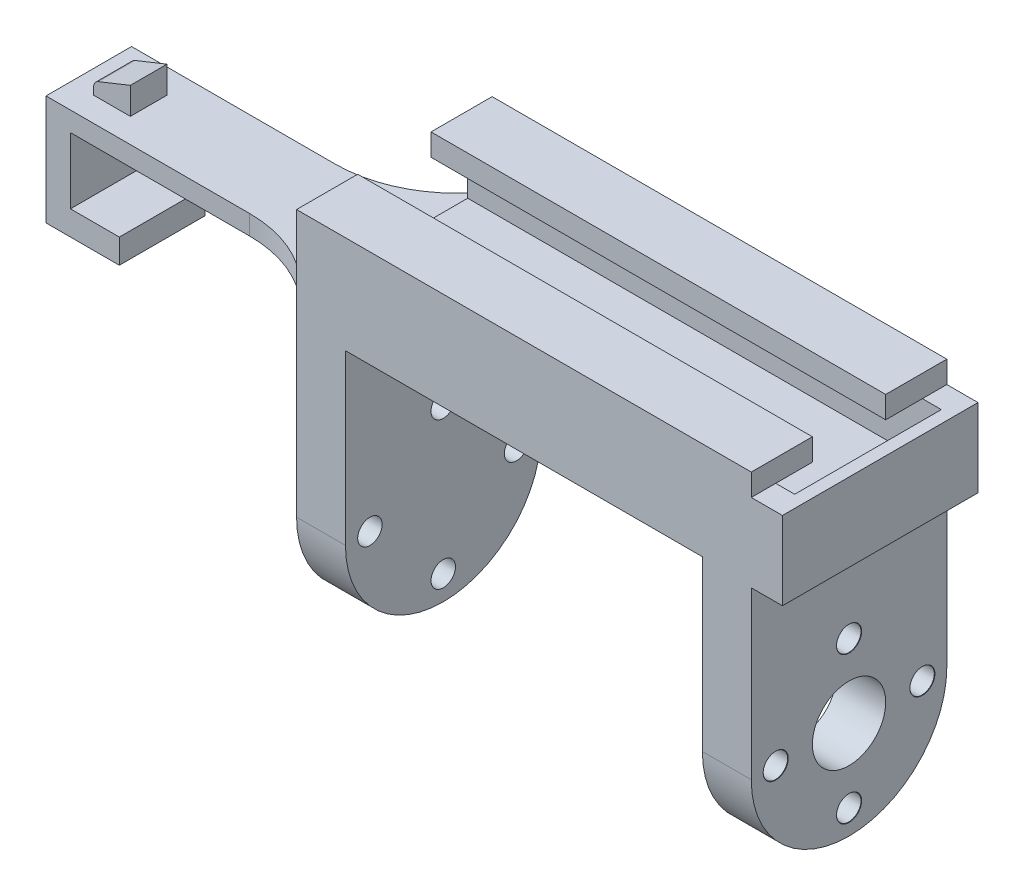
SolidWorks part; units mm, degrees
ref_plane "Front Plane" through (0, 0, 0) normal (0, 0, 1) x (1, 0, 0)
ref_plane "Top Plane" through (0, 0, 0) normal (0, 1, 0) x (1, 0, 0)
ref_plane "Right Plane" through (0, 0, 0) normal (1, 0, 0) x (0, 0, -1)
sketch "Sketch1" plane through (0, 0, 0) normal (0, 0, 1) x (1, 0, 0)
  line L1 (-18.6, 18) -> (18.6, 18)
  line L2 (-18.6, 18) -> (-18.6, -18)
  line L3 (-18.6, -18) -> (18.6, -18)
  line L4 (18.6, 18) -> (18.6, -18)
  line L5 (-18.6, 18) -> (18.6, -18) construction
  line L6 (-18.6, -18) -> (18.6, 18) construction
  line L7 (-14.6, -18) -> (14.6, -18)
  line L8 (-14.6, -18) -> (-14.6, 10)
  line L9 (-14.6, 10) -> (14.6, 10)
  line L10 (14.6, -18) -> (14.6, 10)
  point P0 (0, 0)
  point P10 (0, 10)
  dimension "D1" = 29.2
  dimension "D2" = 4
  dimension "D3" = 28
  dimension "D4" = 8
extrude "Boss-Extrude1" add sketch "Sketch1" along normal blind 8 and the other way blind 8 contours L10 L3 L4 L1 L2 L8 L9 region at (0, 17.4823, 0)
sketch "Sketch2" plane through (18.6, 0, 0) normal (1, 0, 0) x (0, 0, -1)
  circle A0 centre (0, -3.8) radius 6 construction
  point P2 (0, -9.8)
  point P4 (6, -3.8)
  point P5 (0, 2.2)
  point P6 (-6, -3.8)
  dimension "D2" = 12
  dimension "D1" = 3.8
hole_wizard "M1.6 Clearance Hole1" positions "Sketch3" profile "Sketch4" hole size "M1.6" standard "ANSI Metric"
sketch "Sketch3" plane through (18.6, 0, 0) normal (1, 0, 0) x (0, 0, -1)
  point P0 (-6, -3.8)
  point P3 (0, 2.2)
  point P6 (6, -3.8)
  point P9 (0, -9.8)
sketch "Sketch4" plane through (18.6, -3.8, 6) normal (0, 1, 0) x (0, 0, -1)
  line L0 (0, 0) -> (0, 4.6009)
  line L1 (0, 4.6009) -> (1, 4)
  line L2 (1, 4) -> (1, 0.025)
  line L3 (1, 0.025) -> (1.025, 0)
  line L5 (1.025, 0) -> (0, 0)
  line L6 (-1, 0.025) -> (-1.025, 0) construction
  line L10 (0, 4.6009) -> (-1, 4) construction
  line L11 (0, -6.35) -> (0, 107.95) construction
  dimension "Hole Dia." = 2
  dimension "Hole Depth" = 4
  dimension "Near C'Sink Dia." = 2.05
  dimension "Near C'Sink Angle" = 90
  dimension "Drill Angle" = 118
mirror "Mirror1" about plane through (0, 0, 0) normal (1, 0, 0) of "M1.6 Clearance Hole1"
sketch "Sketch5" plane through (18.6, 0, 0) normal (1, 0, 0) x (0, 0, -1)
  line L4 (8, 18) -> (-8, 18)
  line L5 (-8, 18) -> (-8, -18)
  line L6 (-8, -18) -> (8, -18)
  line L7 (8, -18) -> (8, 18)
  line L9 (-8, -3.8) -> (-8, -18)
  line L10 (-8, -18) -> (8, -18)
  line L11 (8, -18) -> (8, -3.8)
  arc A0 (-8, -3.8) -> (8, -3.8) centre (0, -3.8) ccw
  dimension "D1" = 16
  dimension "D2" = 0
extrude "Cut-Extrude1" cut sketch "Sketch5" against normal through all both and the other way through all
sketch "Sketch6" plane through (-18.6, 0, 0) normal (-1, 0, 0) x (0, 0, 1)
  line L0 (-8, 10) -> (8, 10) construction
  line L1 (-8, 10) -> (8, 10) construction
  line L2 (-8, 18) -> (8, 18) construction
  line L3 (-6, 11.8) -> (6, 11.8)
  line L4 (-6, 11.8) -> (-6, 16.2)
  line L5 (-6, 16.2) -> (6, 16.2)
  line L6 (6, 11.8) -> (6, 16.2)
  line L7 (-3, 16.2) -> (3, 16.2)
  line L8 (-3, 16.2) -> (-3, 18)
  line L9 (-3, 18) -> (3, 18)
  line L10 (3, 16.2) -> (3, 18)
  line L11 (8, 18) -> (8, -3.8) construction
  point P12 (0, 11.8)
  point P14 (0, 18)
  line M12 (8, 18) -> (-8, 18)
  dimension "D1" = 2
  dimension "D2" = 1.8
  dimension "D3" = 1.8
  dimension "D4" = 6
extrude "Cut-Extrude2" cut sketch "Sketch6" against normal through all both contours L5 L10 L8 M12 | L3 L6 L5 L4 region at (-18.6, 14, 0) region at (-18.6, 17.1, 0)
sketch "Sketch8" plane through (0, 11.8, 0) normal (0, 1, 0) x (1, 0, 0)
  line L1 (-18.6, -3.5) -> (-41.6, -3.5)
  line L2 (-18.6, -3.5) -> (-18.6, 3.5)
  line L3 (-18.6, 3.5) -> (-41.6, 3.5)
  line L4 (-41.6, -3.5) -> (-41.6, 3.5)
  line L5 (-18.6, 6) -> (-18.6, -6) construction
  point P9 (-18.6, 0)
  point P10 (-18.6, 0)
  dimension "D1" = 7
  dimension "D2" = 23
extrude "Boss-Extrude2" add sketch "Sketch8" against normal blind 1.6 from offset 0.5 contours L4 | L4 region at (-30.1, 11.8, 0) offset against normal yes
sketch "Sketch10" plane through (0, 0, 3.5) normal (0, 0, 1) x (1, 0, 0)
  line L0 (-41.6, 11.3) -> (-43.6, 11.3)
  line L1 (-43.6, 11.3) -> (-43.6, 2.3)
  line L2 (-43.6, 2.3) -> (-37.6, 2.3)
  line L3 (-37.6, 2.3) -> (-37.6, 4.3)
  line L4 (-37.6, 4.3) -> (-41.6, 4.3)
  line L5 (-41.6, 4.3) -> (-41.6, 11.3)
  line L7 (-41.6, 9.7) -> (-41.6, 11.3) construction
  dimension "D1" = 2
  dimension "D2" = 4
  dimension "D3" = 7
extrude "Boss-Extrude3" add sketch "Sketch10" against normal up to surface (7 mm away) up to face at (-30.1, 10.5, -3.5)
sketch "Sketch12" plane through (18.6, 0, 0) normal (1, 0, 0) x (0, 0, -1)
  line L0 (6, 11.8) -> (6, 16.2) construction
  line L1 (6, 11.8) -> (-6, 11.8) construction
  line L2 (-6, 11.8) -> (-6, 16.2) construction
  line L3 (6, 11.8) -> (6, 16.2)
  line L4 (6, 11.8) -> (-6, 11.8)
  line L5 (-6, 11.8) -> (-6, 16.2)
  line L6 (6, 16.2) -> (8, 16.2)
  line L7 (8, 18) -> (8, -3.8) construction
  line L8 (8, 16.2) -> (8, 9.8)
  line L9 (8, 9.8) -> (-8, 9.8)
  line L10 (-8, 18) -> (-8, -3.8) construction
  line L11 (-8, 9.8) -> (-8, 16.2)
  line L12 (-8, 16.2) -> (-6, 16.2)
  dimension "D1" = 2
extrude "Boss-Extrude4" add sketch "Sketch12" along normal offset from surface (1.55 mm away) 0.15 contours L12 L5 L4 L3 L6 L8 L9 L11 offset beyond the face yes
sketch "Sketch13" plane through (20.15, 0, 0) normal (1, 0, 0) x (0, 0, -1)
  line L0 (-8, 16.2) -> (8, 16.2)
  line L8 (-8, 16.2) -> (-8, 9.8)
  line L9 (-8, 9.8) -> (8, 9.8)
  line L10 (8, 9.8) -> (8, 16.2)
  line L11 (8, 16.2) -> (6, 16.2)
  line L12 (6, 16.2) -> (6, 11.8)
  line L13 (6, 11.8) -> (-6, 11.8)
  line L14 (-6, 11.8) -> (-6, 16.2)
  line L15 (-6, 16.2) -> (-8, 16.2)
  line L16 (-8, 16.2) -> (-8, 9.8)
  line L17 (-8, 9.8) -> (8, 9.8)
  line L18 (8, 9.8) -> (8, 16.2)
  dimension "D1" = 0
extrude "Boss-Extrude5" add sketch "Sketch13" along normal blind 1
sketch "Sketch14" plane through (0, 0, 0) normal (0, 0, 1) x (1, 0, 0)
  line L0 (-41.7, 11.3) -> (-41.7, 12.3)
  line L1 (-18.6, 11.3) -> (-43.6, 11.3) construction
  line L2 (-41.7, 12.3) -> (-38.7, 13.5)
  line L3 (-38.7, 13.5) -> (-38.7, 11.3)
  line L4 (-43.6, 11.3) -> (-43.6, 2.3) construction
  line L5 (-38.7, 11.3) -> (-41.7, 11.3)
  dimension "D1" = 2.2
  dimension "D2" = 1.9
  dimension "D3" = 3
  dimension "D4" = 1
extrude "Boss-Extrude6" add sketch "Sketch14" along normal blind 1.5 and the other way blind 1.5
fillet "Fillet1" radius 0.6 1 edges at (-41.7, 12.3, 0)
sketch "Sketch15" plane through (0, 0, 0) normal (0, 0, 1) x (1, 0, 0)
  line L0 (-14.6, -3.8) -> (14.6, -3.8) construction
  point P4 (0, -3.8)
fillet "Fillet2" radius 10 2 edges at (-18.6, 10.5, -3.5) (-18.6, 10.5, 3.5)
fillet "Fillet3" radius 3 1 edges at (-18.6, 9.7, 0)
sketch "Sketch16" plane through (18.6, 0, 0) normal (1, 0, 0) x (0, 0, -1)
  circle A0 centre (0, -3.8) radius 3
  dimension "D1" = 6
extrude "Cut-Extrude3" cut sketch "Sketch16" against normal blind 10 and the other way through all
